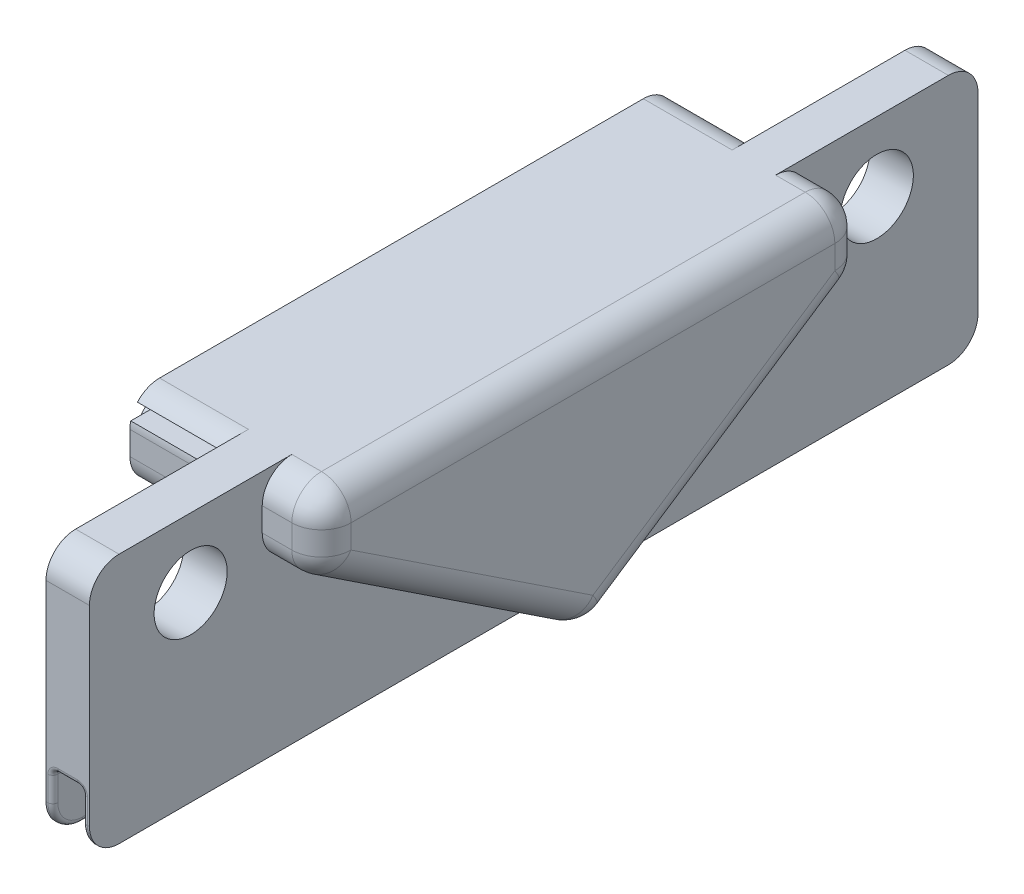
SolidWorks part; units mm, degrees
note: The reader was unsure of these and kept them because the rebuilt part matched: shared geometry of "Sketch7<4>", "Sketch7<5>", "Sketch7<6>".
ref_plane "Front Plane" through (0, 0, 0) normal (0, 0, 1) x (1, 0, 0)
ref_plane "Top Plane" through (0, 0, 0) normal (0, 1, 0) x (1, 0, 0)
ref_plane "Right Plane" through (0, 0, 0) normal (1, 0, 0) x (0, 0, -1)
sketch "Sketch1" plane through (0, 0, 0) normal (0, 1, 0) x (1, 0, 0)
  line L0 (-28.7782, 16.2942) -> (-24.2782, 16.2942)
  line L1 (-24.2782, 16.2942) -> (-24.2782, 25.0442)
  line L2 (-24.2782, 25.0442) -> (-22.0782, 25.0442)
  line L3 (-22.0782, 25.0442) -> (-22.0782, 16.2942)
  line L4 (-22.0782, 16.2942) -> (-19.0782, 16.2942)
  line L5 (-19.0782, 16.2942) -> (-19.0782, 2.5442)
  line L7 (-19.0782, 2.5442) -> (-28.7782, 2.5442)
  line L9 (-28.7782, 2.5442) -> (-28.7782, 16.2942)
  dimension "D1" = 9.7
  dimension "D2" = 3
  dimension "D3" = 8.75
  dimension "D4" = 13.75
extrude "Boss-Extrude1" add sketch "Sketch1" along normal blind 12.7
sketch "Sketch7" plane through (-28.7782, 0, 0) normal (-1, 0, 0) x (0, 0, 1)
  line L0 (-16.2942, 12.7) -> (-16.2942, -1.2986) construction
  line L5 (-16.2942, 12.7) -> (-16.2942, 9.2)
  line L6 (-13.0442, 12.0986) -> (-13.0442, 6.3014) construction
  line L7 (-13.0442, 9.2) -> (-15.8582, 9.2) construction
  line L8 (-16.2942, 9.2) -> (-2.5442, 0.0973)
  line L9 (-2.5442, 0.0973) -> (-2.5442, 12.7)
  line L10 (-2.5442, 12.7) -> (-16.2942, 12.7)
  line L11 (-2.5442, 12.2) -> (-16.2942, 12.2)
  line L12 (-16.2942, 12.2) -> (-16.2942, 11.55)
  line L13 (-16.2942, 9.2) -> (-16.2942, 0)
  line L14 (-16.2942, 11.55) -> (-2.5442, 11.55)
  line L15 (-2.5442, 11.55) -> (-2.5442, 12.2)
  line L16 (-16.2942, 0) -> (-2.5442, 0)
  line L17 (-2.5442, 0) -> (-2.5442, 0.0973)
  line L18 (-2.5442, 0.0973) -> (-16.2942, 9.2)
  line L19 (-16.2942, 0) -> (-16.2942, 9.2)
  line L20 (-16.2942, 9.2) -> (-23.5442, 9.2) construction
  line L23 (-21.0442, 12.7) -> (-21.0442, 0) construction
  line L24 (-25.0442, 12.7) -> (-16.2942, 12.7) construction
  line L25 (-25.0442, 0) -> (-16.2942, 0) construction
  line L26 (-25.0442, 12.7) -> (-25.0442, 0) construction
  circle A0 centre (-13.0442, 9.2) radius 1.6
  circle A1 centre (-19.9192, 9.2) radius 1.85
  line M20 (-16.2942, 0) -> (-2.5442, 0)
  line M21 (-2.5442, 0) -> (-2.5442, 12.7)
  line M23 (-16.2942, 12.7) -> (-16.2942, 0)
  dimension "D1" = 13.75
  dimension "D2" = 0.5
  dimension "D3" = 12.6027
  dimension "D4" = 3.5
  dimension "D5" = 3.25
  dimension "D6" = 0.65
  dimension "D7" = 3.5
  dimension "D8" = 4
extrude "Cut-Extrude2" cut sketch "Sketch7" against normal blind 4 contours L15 L11 L12 L14
extrude "Boss-Extrude2" add sketch "Sketch7<4>" along normal blind 1.4 contours A0
sketch "Sketch7<4>" plane through (-28.7782, 0, 0) normal (-1, 0, 0) x (0, 0, 1) same geometry as "Sketch7"
extrude "Cut-Extrude3" cut sketch "Sketch7<5>" against normal up to surface (4.5 mm away) contours L8 M23 M20 M21 up to face at (-24.2782, 6.35, -20.6692)
sketch "Sketch7<5>" plane through (-28.7782, 0, 0) normal (-1, 0, 0) x (0, 0, 1) same geometry as "Sketch7"
extrude "Cut-Extrude4" cut sketch "Sketch7<6>" against normal through all and the other way through all contours A1
sketch "Sketch7<6>" plane through (-28.7782, 0, 0) normal (-1, 0, 0) x (0, 0, 1) same geometry as "Sketch7"
sketch "Sketch10" plane through (-22.0782, 0, 0) normal (1, 0, 0) x (0, 0, -1)
  line L1 (16.2942, 9.2) -> (16.2942, 0)
  line L3 (16.2942, 0) -> (2.5442, 0)
  line L4 (2.5442, 0) -> (2.5442, 0.0973)
  line L7 (2.5442, 0.0973) -> (16.2942, 9.2)
  dimension "D1" = 13.75
  dimension "D2" = 9.2
extrude "Cut-Extrude5" cut sketch "Sketch10" along normal up to surface (3 mm away) from surface
sketch "Sketch12" plane through (0, 0, 0) normal (0, -1, 0) x (1, 0, 0)
  line L0 (-23.1782, -25.0442) -> (-23.1782, -2.5442) construction
  line L1 (-22.0782, -2.5442) -> (-22.0782, -25.0442) construction
  line L3 (-22.0782, -25.0442) -> (-24.2782, -25.0442) construction
  line L12 (-23.9282, -2.5442) -> (-22.4282, -2.5442)
  line L13 (-23.9282, -2.5442) -> (-23.9282, -25.0442)
  line L14 (-23.9282, -25.0442) -> (-22.4282, -25.0442)
  line L15 (-22.4282, -2.5442) -> (-22.4282, -25.0442)
  line L16 (-23.9282, -2.5442) -> (-22.4282, -25.0442) construction
  line L17 (-23.9282, -25.0442) -> (-22.4282, -2.5442) construction
  point P6 (-23.1782, -2.5442)
  point P11 (-23.1782, -13.7942)
  dimension "D1" = 0.75
extrude "Cut-Extrude6" cut sketch "Sketch12" against normal blind 3
sketch "Sketch14" plane through (0, 0, 0) normal (0, -1, 0) x (-1, 0, 0)
  line L1 (24.2782, 2.5442) -> (22.0782, 2.5442)
  line L2 (24.2782, 2.5442) -> (24.2782, 6.5442)
  line L3 (24.2782, 6.5442) -> (22.0782, 6.5442)
  line L4 (22.0782, 2.5442) -> (22.0782, 6.5442)
  line L5 (24.2782, 25.0442) -> (24.2782, 2.5442) construction
  line L6 (22.0782, 16.2942) -> (22.0782, 2.5442) construction
  dimension "D1" = 4
extrude "Boss-Extrude3" add sketch "Sketch14" against normal blind 1
mirror "Mirror3" about plane through (-19.0782, 12.7, -2.5442) normal (0, 0, -1) of bodies 110
fillet "Fillet5" radius 1.5 26 edges at (-19.0782, 12.7, -2.5442) (-19.0782, 10.95, -16.2942) (-26.5282, 12.7, 11.2058) (-24.7782, 11.875, 11.2058) (-26.7782, 11.55, 11.2058) (-19.0782, 10.95, 11.2058) (-19.0782, 4.6487, 4.3308) (-20.5782, 12.7, 11.2058) (-20.5782, 9.2, 11.2058) (-23.1782, 12.7, 19.9558) (-24.1032, 0, 19.9558) (-22.2532, 0, 19.9558) (-26.7782, 12.2, 11.2058) (-26.5282, 9.2, 11.2058) (-20.5782, 0.0973, -2.5442) (-20.5782, 12.7, -16.2942) (-23.1782, 12.7, -25.0442) (-24.7782, 11.875, -16.2942) (-26.7782, 11.55, -16.2942) (-26.7782, 12.2, -16.2942) (-26.5282, 12.7, -16.2942) (-26.5282, 9.2, -16.2942) (-19.0782, 4.6487, -9.4192) (-20.5782, 9.2, -16.2942) (-24.1032, 0, -25.0442) (-22.2532, 0, -25.0442)
fillet "Fillet6" radius 0.25 26 edges at (-23.1782, 0, -6.5442) (-23.1782, 1, -6.5442) (-23.1782, 0, 1.4558) (-23.9282, 0, -15.0442) (-22.4282, 0, -15.0442) (-23.9282, 0, 9.9558) (-22.4282, 0, 9.9558) (-23.9282, 0.4393, -24.6049) (-22.4282, 0.4393, -24.6049) (-23.9282, 0.4393, 19.5165) (-22.4282, 0.4393, 19.5165) (-23.9282, 0.5, -6.5442) (-22.4282, 0.5, -6.5442) (-22.4282, 0.5, 1.4558) (-23.1782, 1, 1.4558) (-23.9282, 0.5, 1.4558) (-23.9282, 2.25, -25.0442) (-22.4282, 2.25, -25.0442) (-23.9282, 2.25, 19.9558) (-22.4282, 2.25, 19.9558) (-23.9282, 1, -2.5442) (-22.4282, 1, -2.5442) (-23.1782, 3, -25.0442) (-23.9282, 3, -2.5442) (-23.1782, 3, 19.9558) (-22.4282, 3, -2.5442)
